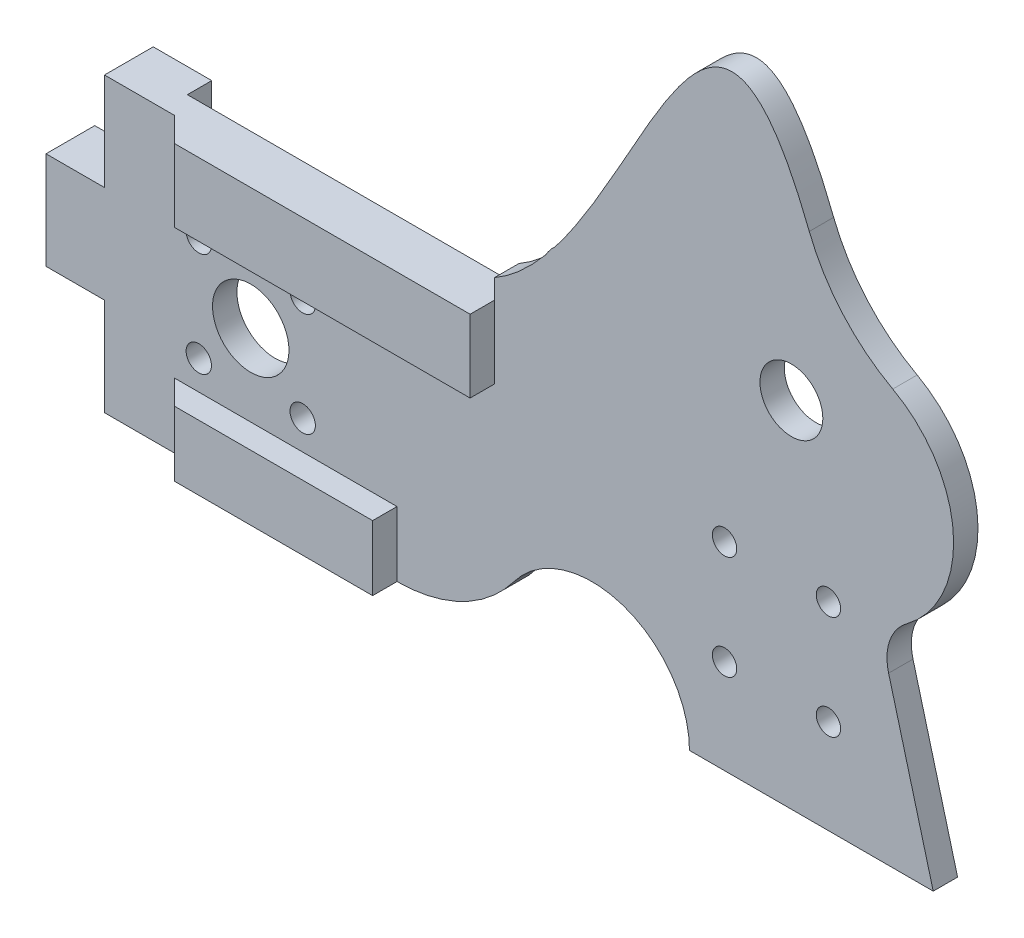
SolidWorks part; units mm, degrees
ref_plane "Front Plane" through (0, 0, 0) normal (0, 0, 1) x (1, 0, 0)
ref_plane "Top Plane" through (0, 0, 0) normal (0, 1, 0) x (1, 0, 0)
ref_plane "Right Plane" through (0, 0, 0) normal (1, 0, 0) x (0, 0, -1)
sketch "Sketch1" plane through (0, 0, 0) normal (0, 0, 1) x (1, 0, 0)
  line L0 (0, 0) -> (107.95, 0)
  line L3 (0, 38.1) -> (0, 25.4)
  line L4 (95.3675, 55.88) -> (0, 38.1)
  line L5 (0, 19.05) -> (100.2273, 19.05) construction
  line L6 (19.05, 19.05) -> (19.05, 28.62) construction
  line L7 (19.05, 19.05) -> (25.817, 25.817) construction
  line L8 (107.95, 0) -> (100.9363, 26.1756)
  line L10 (0, 12.7) -> (0, 0)
  line L11 (0, 25.4) -> (-7.62, 25.4)
  line L13 (0, 12.7) -> (-7.62, 12.7)
  line L14 (-7.62, 25.4) -> (-7.62, 12.7)
  line L15 (100.9363, 26.1756) -> (100.8688, 26.4276)
  arc A0 (100.8688, 26.4276) -> (95.3675, 55.88) centre (95.3675, 40.64) ccw
  circle A1 centre (95.3675, 40.64) radius 4.0957 construction
  circle A2 centre (19.05, 19.05) radius 9.57 construction
  circle A3 centre (25.817, 25.817) radius 1.651
  circle A4 centre (25.817, 12.283) radius 1.651
  circle A5 centre (12.283, 12.283) radius 1.651
  circle A6 centre (12.283, 25.817) radius 1.651
  point P26 (19.05, 19.05)
  dimension "D1" = 8.1915
  dimension "D5" = 15.24
  dimension "D4" = 19.14
  dimension "D7" = 3.302
  dimension "D11" = 97.0107
  dimension "D2" = 38.1
  dimension "D3" = 40.64
  dimension "D6" = 107.95
  dimension "D8" = 45
  dimension "D9" = 4
  dimension "D10" = 19.05
  dimension "D12" = 75
  dimension "D14" = 12.7
  dimension "D15" = 12.7
  dimension "D16" = 7.62
extrude "Boss-Extrude1" add sketch "Sketch1" along normal blind 3.175
sketch "Sketch2" plane through (0, 0, 3.175) normal (0, 0, 1) x (1, 0, 0)
  circle A0 centre (95.3675, 40.64) radius 38.1 construction
sketch "Sketch6" plane through (0, 0, 3.175) normal (0, 0, 1) x (1, 0, 0)
  line L0 (0, 0) -> (107.95, 0) construction
  line L1 (50.8, 0) -> (76.2, 0)
  arc A0 (76.2, 0) -> (50.8, 0) centre (63.5, 0) ccw
  dimension "D1" = 25.4
  dimension "D2" = 31.75
extrude "Cut-Extrude2" cut sketch "Sketch6" against normal blind 6.35
sketch "Sketch7" plane through (0, 0, 3.175) normal (0, 0, 1) x (1, 0, 0)
  line L0 (12.283, 25.817) -> (25.817, 12.283) construction
  line L1 (12.283, 12.283) -> (25.817, 25.817) construction
  line L2 (12.283, 25.817) -> (78.4839, 25.817) construction
  line L3 (11.7326, 12.283) -> (12.283, 12.283) construction
  circle A0 centre (19.05, 19.05) radius 4.9784
  circle A4 centre (80.7666, 12.283) radius 1.5875
  circle A5 centre (94.2997, 12.283) radius 1.5875
  circle A6 centre (80.7666, 25.817) radius 1.5875
  circle A7 centre (94.2997, 25.817) radius 1.5875
  dimension "D1" = 9.9568
  dimension "D2" = 3.175
  dimension "D3" = 13.5331
extrude "Cut-Extrude3" cut sketch "Sketch7" against normal through all
fillet "Fillet1" radius 6.35 1 edges at (100.8688, 26.4276, 1.5875)
sketch "Sketch8" plane through (0, 0, 3.175) normal (0, 0, 1) x (1, 0, 0)
  line L1 (0, 38.1) -> (50.8, 38.1)
  line L2 (0, 38.1) -> (0, 50.8)
  line L3 (0, 50.8) -> (50.8, 50.8)
  line L4 (50.8, 38.1) -> (50.8, 50.8)
  dimension "D1" = 50.8
  dimension "D2" = 12.7
extrude "Cut-Extrude4" cut sketch "Sketch8" against normal blind 50.8
sketch "Sketch9" plane through (0, 0, 3.175) normal (0, 0, 1) x (1, 0, 0)
  line L3 (50.8, 40.64) -> (57.15, 40.64)
  line L5 (57.15, 40.64) -> (50.8, 40.64)
  line L6 (57.15, 40.64) -> (57.15, 50.8)
  line L7 (57.15, 50.8) -> (50.8, 50.8)
  line L8 (50.8, 40.64) -> (50.8, 50.8)
  line L9 (0, 38.1) -> (50.8, 38.1) construction
  line M8 (50.8, 47.571) -> (50.8, 38.1)
  line M21 (95.3675, 55.88) -> (50.8, 47.571)
  dimension "D1" = 10.16
  dimension "D2" = 2.54
  dimension "D3" = 6.35
extrude "Cut-Extrude5" cut sketch "Sketch9" against normal blind 19.304 contours L3 L6 M21 M8 region at (54.0583, 44.4092, 3.175)
fillet "Fillet6" radius 6.35 1 edges at (57.15, 40.64, 1.5875)
fillet "Fillet7" radius 6.35 1 edges at (57.15, 48.7549, 1.5875)
fillet "Fillet8" radius 19.05 1 edges at (50.8, 0, 1.5875)
sketch "Sketch12" plane through (0, 0, 3.175) normal (0, 0, 1) x (1, 0, 0)
  line L0 (107.95, 0) -> (146.812, 0) construction
  line L1 (8.0257, 45.4128) -> (80.6683, 75.7903) construction
  line L2 (95.3675, 40.64) -> (80.6683, 75.7903) construction
  line L3 (80.6683, 75.7903) -> (79.4434, 78.7195) construction
  line L4 (50.8, 40.64) -> (85.0271, 40.64)
  line L5 (85.0271, 40.64) -> (95.3675, 55.88)
  arc A0 (61.8128, 49.6242) -> (56.8883, 45.1859) centre (62.9766, 43.3817) ccw construction
  circle A1 centre (19.05, 19.05) radius 28.575 construction
  circle A2 centre (95.3675, 40.64) radius 38.1 construction
  circle A3 centre (80.6683, 75.7903) radius 3.175 construction
  spline S0 degree 3 poles (50.8, 40.64) (70.7778, 52.1788) (78.5943, 111.5434) (95.3675, 55.88) knots 0 0 0 0 1 1 1 1
  dimension "D2" = 6.35
  dimension "D1" = 38.862
extrude "Boss-Extrude2" add sketch "Sketch12" against normal blind 3.175
fillet "Fillet9" radius 24.13 1 edges at (95.3675, 55.88, 1.5875)
sketch "Sketch13" plane through (0, 0, 0) normal (0, 0, -1) x (-1, 0, 0)
  line L1 (-50.8, 38.1) -> (-9.1321, 38.1)
  line L2 (-50.8, 38.1) -> (-50.8, 28.6404)
  line L3 (-50.8, 28.6404) -> (-9.1321, 28.6404)
  line L6 (-9.1321, 8.4682) -> (-38.1, 8.4682)
  line L7 (-9.1321, 8.4682) -> (-9.1321, 0)
  line L8 (-9.1321, 0) -> (-38.1, 0)
  line L9 (-38.1, 8.4682) -> (-38.1, 0)
  line L10 (-9.1321, 38.1) -> (-9.1321, 28.6404)
extrude "Boss-Extrude3" add sketch "Sketch13" against normal blind 6.35
sketch "Sketch16" plane through (0, 0, 3.175) normal (0, 0, 1) x (1, 0, 0)
  circle A0 centre (89.4737, 46.137) radius 4.0958
  circle A1 centre (94.2997, 25.817) radius 1.5875 construction
  dimension "D1" = 20.32
  dimension "D2" = 4.826
extrude "Cut-Extrude8" cut sketch "Sketch16" against normal through all
sketch "Sketch18" plane through (0, 0, 3.175) normal (0, 0, 1) x (1, 0, 0)
  line L0 (0, 0) -> (7.62, 0)
  line L1 (0, 0) -> (9.1321, 0) construction
  line L2 (7.62, 0) -> (7.62, 38.1)
  line L3 (0, 38.1) -> (9.1321, 38.1) construction
  line L4 (7.62, 38.1) -> (0, 38.1)
  line L5 (0, 38.1) -> (0, 25.4)
  line L6 (0, 25.4) -> (-7.62, 25.4)
  line L7 (-7.62, 25.4) -> (-7.62, 12.7)
  line L8 (-7.62, 12.7) -> (0, 12.7)
  line L9 (0, 12.7) -> (0, 0)
  dimension "D1" = 7.62
extrude "Boss-Extrude4" add sketch "Sketch18" against normal blind 6.35
sketch "Sketch19" plane through (0, 38.1, 0) normal (0, 1, 0) x (1, 0, 0)
  line L0 (9.1321, -3.175) -> (12.3071, -6.35)
  line L1 (9.1321, -6.35) -> (9.1321, -3.175) construction
  line L2 (0, -3.175) -> (9.1321, -3.175) construction
  line L3 (9.1321, -6.35) -> (50.8, -6.35) construction
  line L4 (12.3071, -6.35) -> (9.1321, -6.35)
  line L5 (9.1321, -6.35) -> (9.1321, -3.175)
  dimension "D1" = 45
extrude "Cut-Extrude9" cut sketch "Sketch19" against normal through all
